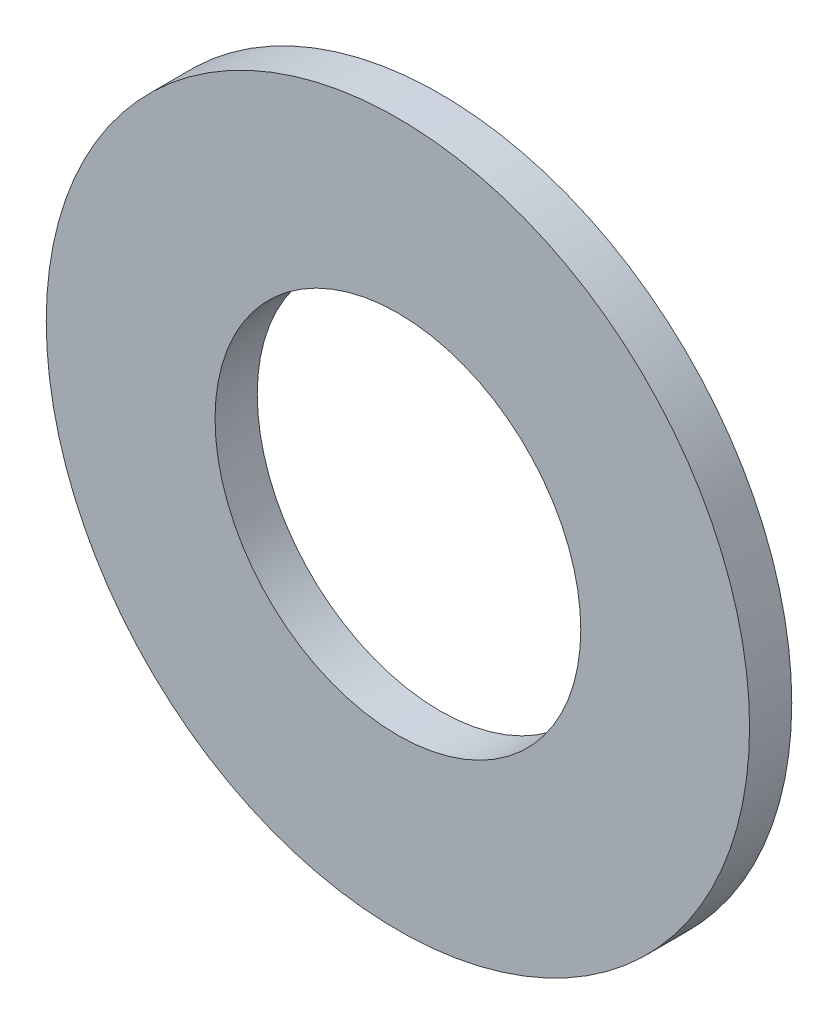
SolidWorks part; units mm, degrees
material "Alloy Steel"
ref_plane "Plane1" through (0, 0, 0) normal (0, 0, 1) x (1, 0, 0)
ref_plane "Plane2" through (0, 0, 0) normal (0, 1, 0) x (1, 0, 0)
ref_plane "Plane3" through (0, 0, 0) normal (1, 0, 0) x (0, 0, -1)
ref_axis "Axis1" through (-83.9706, 0, 0) along (1, 0, 0)
ref_axis "Axis2" through (0, 0, -0.0826) along (0, 0, 1)
ref_axis "Axis3" through (0, 8.7312, 0) along (0, -1, 0)
sketch "Sketch1" plane through (0, 0, 0) normal (0, 0, 1) x (1, 0, 0)
  circle A0 centre (0, 0) radius 3.302
  circle A1 centre (0, 0) radius 6.35
  dimension "D1" = 6.604
  dimension "D2" = 12.7
extrude "Boss-Extrude1" add sketch "Sketch1" along normal blind 0.762
equation "\"id\"= 0.26"
equation "\"od\"= 0.5"
equation "\"thk\"= 0.03"
equation "\"D1@Sketch1\" = \"id\""
equation "\"D2@Sketch1\" = \"od\""
equation "\"D1@Boss-Extrude1\" = \"thk\""
